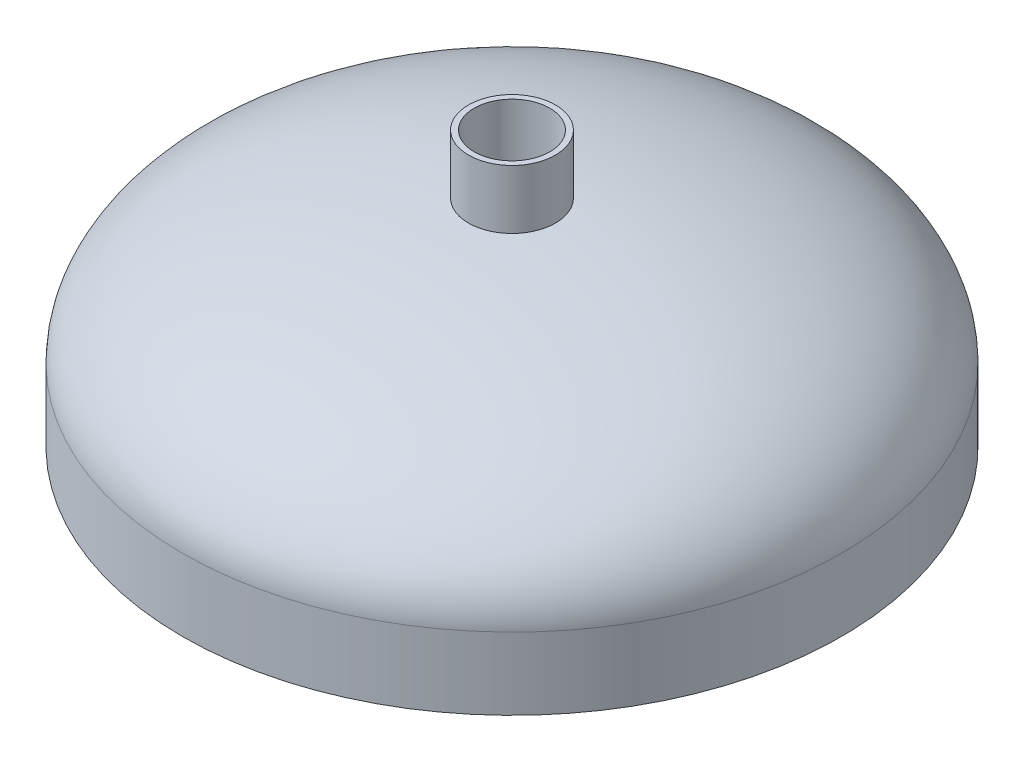
SolidWorks part; units mm, degrees
material "ASTM A36 Acero"
ref_plane "Alzado" through (0, 0, 0) normal (0, 0, 1) x (1, 0, 0)
ref_plane "Planta" through (0, 0, 0) normal (0, 1, 0) x (1, 0, 0)
ref_plane "Vista lateral" through (0, 0, 0) normal (1, 0, 0) x (0, 0, -1)
sketch "Croquis1" plane through (0, 0, 0) normal (0, 1, 0) x (1, 0, 0)
  circle A0 centre (0, 0) radius 228.6
  dimension "D1" = 457.2
extrude "Saliente-Extruir1" add sketch "Croquis1" along normal blind 50
dome "Cúpula1" faces to dome 1 distance 100 reverse direction no elliptical dome yes face at (0, 50, 228.6) parameters "D1"=100
shell "Vaciado1" thickness 9.525 removed face at (0, 0, 228.6)
ref_plane "Plano1" through (0, 150, 0) normal (0, 1, 0) x (1, 0, 0)
ref_plane "Plano2" through (0, 190, 0) normal (0, 1, 0) x (1, 0, 0)
sketch "Croquis3" plane through (0, 190, 0) normal (0, 1, 0) x (1, 0, 0)
  circle A0 centre (0, 0) radius 30.15
  dimension "D1" = 60.3
extrude "Saliente-Extruir2" add sketch "Croquis3" against normal blind 60
sketch "Croquis4" plane through (0, 190, 0) normal (0, 1, 0) x (1, 0, 0)
  circle A0 centre (0, 0) radius 26.24
  dimension "D1" = 52.48
extrude "Cortar-Extruir1" cut sketch "Croquis4" against normal up to next
